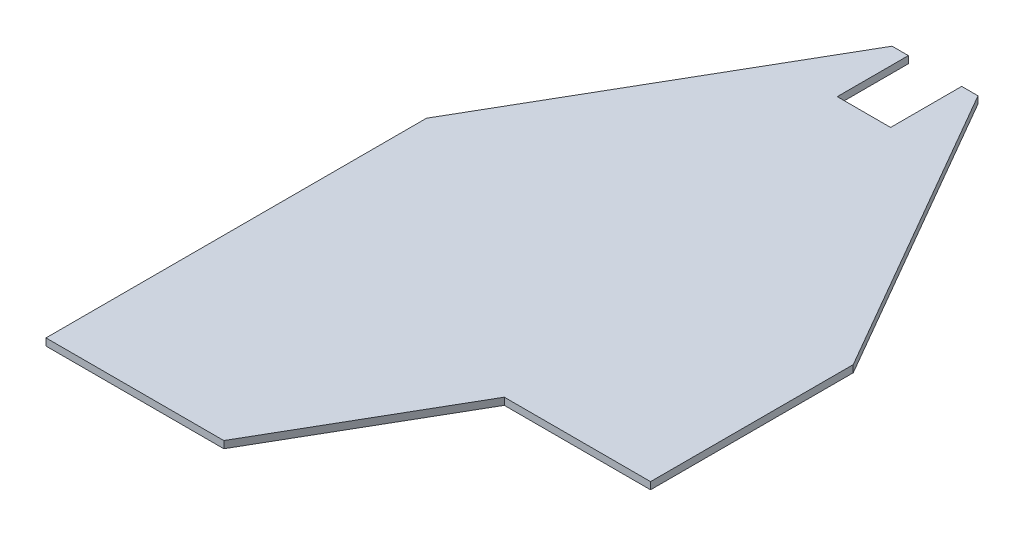
SolidWorks part; units mm, degrees
material "1.0116 (S235J2G3)"
ref_plane "Front Plane" through (0, 0, 0) normal (0, 0, 1) x (1, 0, 0)
ref_plane "Top Plane" through (0, 0, 0) normal (0, 1, 0) x (1, 0, 0)
ref_plane "Right Plane" through (0, 0, 0) normal (1, 0, 0) x (0, 0, -1)
sketch "Sketch1" plane through (0, 0, 0) normal (0, 1, 0) x (1, 0, 0)
  line L0 (0, 0) -> (0, 1800) construction
  line L1 (600, 0) -> (188.6751, 0)
  line L2 (-600, 0) -> (-600, 570)
  line L3 (-600, 570) -> (-120.7993, 1400)
  line L4 (-120.7993, 1400) -> (-75, 1400)
  line L5 (-75, 1400) -> (-75, 1200)
  line L6 (-75, 1200) -> (75, 1200)
  line L7 (75, 1400) -> (75, 1200)
  line L8 (120.7993, 1400) -> (75, 1400)
  line L9 (600, 570) -> (120.7993, 1400)
  line L10 (600, 0) -> (600, 570)
  line L11 (-600, 0) -> (-600, -500)
  line L12 (-600, -500) -> (-100, -500)
  line L13 (-100, -500) -> (188.6751, 0)
  point P3 (-97.8996, 1400)
  point P11 (0, 1200)
  dimension "D1" = 1800
  dimension "D2" = 600
  dimension "D3" = 570
  dimension "D4" = 1400
  dimension "D5" = 75
  dimension "D6" = 60
  dimension "D7" = 200
  dimension "D8" = 500
  dimension "D9" = 500
  dimension "D10" = 120
  dimension "D11" = 411.3249
extrude "Boss-Extrude2" add sketch "Sketch1" along normal blind 20
